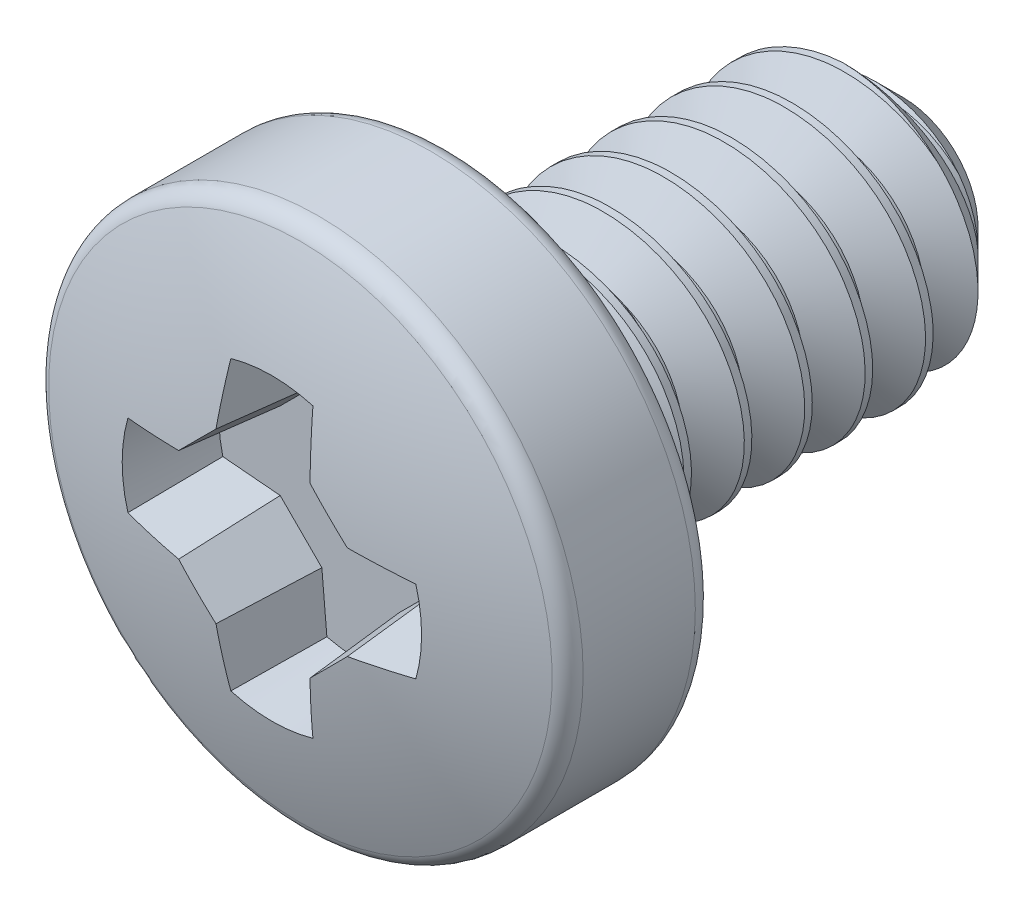
SolidWorks part; units mm, degrees
ref_plane "Front Plane" through (0, 0, 0) normal (0, 0, 1) x (1, 0, 0)
ref_plane "Top Plane" through (0, 0, 0) normal (0, 1, 0) x (1, 0, 0)
ref_plane "Right Plane" through (0, 0, 0) normal (1, 0, 0) x (0, 0, -1)
sketch "Sketch1" plane through (0, 0, 0) normal (1, 0, 0) x (0, 0, -1)
  line L0 (-1.3652, -2.7813) -> (-1.3652, 0) construction
  line L1 (3.3972, -1.4224) -> (3.3972, 1.4224) construction
  line L2 (3.3972, 0) -> (-3.3972, 0) construction
  line L3 (-2.8892, 2.7813) -> (-1.3652, 2.7813)
  line L4 (-2.8892, -2.7813) -> (-1.3652, -2.7813)
  line L5 (3.3972, 1.4224) -> (-1.3652, 1.4224) construction
  line L6 (3.3972, -1.4224) -> (2.7622, -1.4224) construction
  line L7 (-1.3652, 0) -> (-1.3652, 2.7813) construction
  arc A0 (-2.8892, -2.7813) -> (-2.8892, 2.7813) centre (4.4706, 0) cw
  point P3 (0, 0)
  point P4 (0, 0)
  point P8 (3.3972, 0)
  point P13 (1.8097, -1.4224)
  point P16 (2.7622, -1.4224)
  point P17 (-2.305, 0)
  point P18 (-2.0002, 0)
  dimension "Head Diameter" = 5.5626
  dimension "Head Height" = 2.032
  dimension "Screw Size Decimal Equivalent" = 2.8448
  dimension "Thread Pitch" = 0.635
  dimension "D3" = 1.5875
  dimension "D2" = 0.635
  dimension "D4" = 0.3048
  dimension "D5" = 5.3975
  dimension "Length" = 4.7625
sketch "Sketch2" plane through (0, 0, 0) normal (1, 0, 0) x (0, 0, -1)
  line L0 (-2.8892, 2.7813) -> (-1.3652, 2.7813)
  line L1 (-1.3652, 2.7813) -> (-1.3652, 1.4224)
  line L2 (-1.3652, 1.4224) -> (3.3972, 1.4224)
  line L3 (3.3972, 1.4224) -> (3.3972, 0)
  line L4 (3.3972, -1.4224) -> (3.3972, 1.4224) construction
  line L5 (3.3972, 0) -> (-3.3972, 0)
  arc A0 (-3.3972, 0) -> (-2.8892, 2.7813) centre (4.4706, 0) cw
  arc A1 (-2.8892, 2.7813) -> (-2.8892, -2.7813) centre (4.4706, 0) ccw construction
revolve "Revolve1" add sketch "Sketch2" angle 360 about L5
ref_plane "Plane1" through (0, 0, 3.3972) normal (0, 0, 1) x (1, 0, 0)
sketch "Sketch3" plane through (0, 0, 3.3972) normal (0, 0, 1) x (1, 0, 0)
  line L0 (0, 0) -> (0, 0.889) construction
  line L1 (0, -2.7813) -> (0, 2.7813) construction
  line L2 (-0.4445, 0) -> (0.4445, 0) construction
  line L3 (0, 0) -> (1.5875, 0) construction
  line L4 (0.4445, 1.524) -> (0.5001, 0.889)
  line L5 (0.889, 0.5001) -> (1.524, 0.4445)
  line L6 (0, 0) -> (0.6286, 0.6286) construction
  line L7 (0.5001, 0.889) -> (0.889, 0.5001)
  line L8 (0.6945, 0.6945) -> (0.6286, 0.6286) construction
  line L9 (0.4445, 1.524) -> (0.4445, 0.7699) construction
  line L10 (0.889, -0.5001) -> (1.524, -0.4445)
  line L11 (0.5001, -0.889) -> (0.889, -0.5001)
  line L12 (0.4445, -1.524) -> (0.5001, -0.889)
  line L13 (-0.4445, -1.524) -> (-0.5001, -0.889)
  line L14 (-0.5001, -0.889) -> (-0.889, -0.5001)
  line L15 (-0.889, -0.5001) -> (-1.524, -0.4445)
  line L16 (-0.889, 0.5001) -> (-1.524, 0.4445)
  line L17 (-0.5001, 0.889) -> (-0.889, 0.5001)
  line L18 (-0.4445, 1.524) -> (-0.5001, 0.889)
  circle A0 centre (0, 0) radius 1.5875 construction
  circle A1 centre (0, 0) radius 0.889 construction
  arc A2 (-0.4445, 1.524) -> (0.4445, 1.524) centre (0, 0) cw
  arc A3 (1.524, 0.4445) -> (1.524, -0.4445) centre (0, 0) cw
  arc A4 (-1.524, 0.4445) -> (-1.524, -0.4445) centre (0, 0) ccw
  arc A5 (-0.4445, -1.524) -> (0.4445, -1.524) centre (0, 0) ccw
  point P9 (0, 0)
  point P21 (0, -1.5875)
  dimension "Phil_DIA" = 3.175
  dimension "Phil_W" = 0.889
  dimension "D1" = 45
  dimension "D2" = 0.889
extrude "Cut-Extrude1" cut sketch "Sketch3" against normal up to vertex (1.0922 mm away) draft 5 up to point (0, 0, 2.305)
fillet "Fillet1" radius 0.2032 2 edges at (0, 2.7813, 1.3652) (0, 2.7813, 2.8892)
chamfer "Chamfer1" distance 0.635 angle 45 1 edges at (0, 1.4224, -3.3972)
sketch "Sketch4" plane through (0, 0, 0) normal (1, 0, 0) x (0, 0, -1)
  line L0 (3.3576, 1.4911) -> (3.9926, 1.4911) construction
  line L1 (3.9926, 1.4911) -> (3.6751, 0.9412) construction
  line L2 (3.6751, 0.9412) -> (3.3576, 1.4911) construction
  line L3 (3.6751, 0.9412) -> (3.6751, 1.01) construction
  line L4 (3.6751, 1.01) -> (3.6751, 1.4224) construction
  line L5 (3.6751, 1.4224) -> (3.6751, 1.4911) construction
  line L6 (3.9727, 1.4568) -> (3.3774, 1.4568) construction
  line L7 (3.9529, 1.4224) -> (3.3972, 1.4224) construction
  line L8 (3.7147, 1.01) -> (3.6354, 1.01) construction
  line L9 (3.3774, 1.4568) -> (3.9727, 1.4568)
  line L10 (3.9727, 1.4568) -> (3.7147, 1.01)
  line L11 (3.7147, 1.01) -> (3.6354, 1.01)
  line L12 (3.6354, 1.01) -> (3.3774, 1.4568)
  line L13 (3.3972, -1.4224) -> (3.3972, 1.4224) construction
  line L14 (3.3972, 1.4224) -> (-1.3652, 1.4224) construction
  point P9 (3.6751, 1.4224)
  point P12 (3.6751, 1.4568)
  point P15 (3.6751, 1.01)
  dimension "D1" = 0.635
  dimension "D2" = 0.0794
sketch "Sketch5" plane through (0, 0, -3.3972) normal (0, 0, -1) x (-1, 0, 0)
  circle A0 centre (0, 0) radius 1.4224
curve "Helix/Spiral1" pitch 0.635 height 5.3975 radius 1.4224 centre (0, 0, -3.3972) axis (0, 0, 1) start towards (0, 1, 0)
sweep "Cut-Sweep1" cut profiles "Sketch4" path "Helix/Spiral1" align with end faces yes
sketch "Sketch6" plane through (0, 0, 1.3652) normal (0, 0, -1) x (-1, 0, 0)
  circle A0 centre (0, 0) radius 2.5781
  circle A1 centre (0, 0) radius 2.5781 construction
extrude "Boss-Extrude1" add sketch "Sketch6" against normal up to surface (0.9398 mm away) up to face at (0, 0, 2.305)
sketch "Sketch7" plane through (0, 0, 1.3652) normal (0, 0, -1) x (-1, 0, 0)
  line L0 (0, 2.7813) -> (0, -2.7813) construction
  circle A0 centre (0, 0) radius 1.4911
extrude "Boss-Extrude2" add sketch "Sketch7" along normal up to vertex (4.7625 mm away) draft 20 up to point (0, 0, -3.3972)
equation "\"D1@Sketch1\" = \"Head Height@Sketch1\" * 0.75"
equation "\"D3@Sketch1\"=\"Thread Pitch@Sketch1\" * 2.5"
equation "\"D2@Sketch1\" = \"Thread Pitch@Sketch1\""
equation "\"D4@Sketch1\" = \"D1@Sketch1\" / 5"
equation "\"D2@Sketch3\"=\"Phil_W@Sketch3\""
equation "\"D1@Fillet1\" = \"Head Height@Sketch1\" / 10"
equation "\"D1@Chamfer1\" = \"Thread Pitch@Sketch1\""
equation "\"D1@Sketch4\" = \"Thread Pitch@Sketch1\""
equation "\"D2@Sketch4\"=\"D1@Sketch4\"/8"
equation "\"D4@Helix/Spiral1\" = \"Thread Pitch@Sketch1\""
equation "\"D3@Helix/Spiral1\" = \"D5@Sketch1\""
